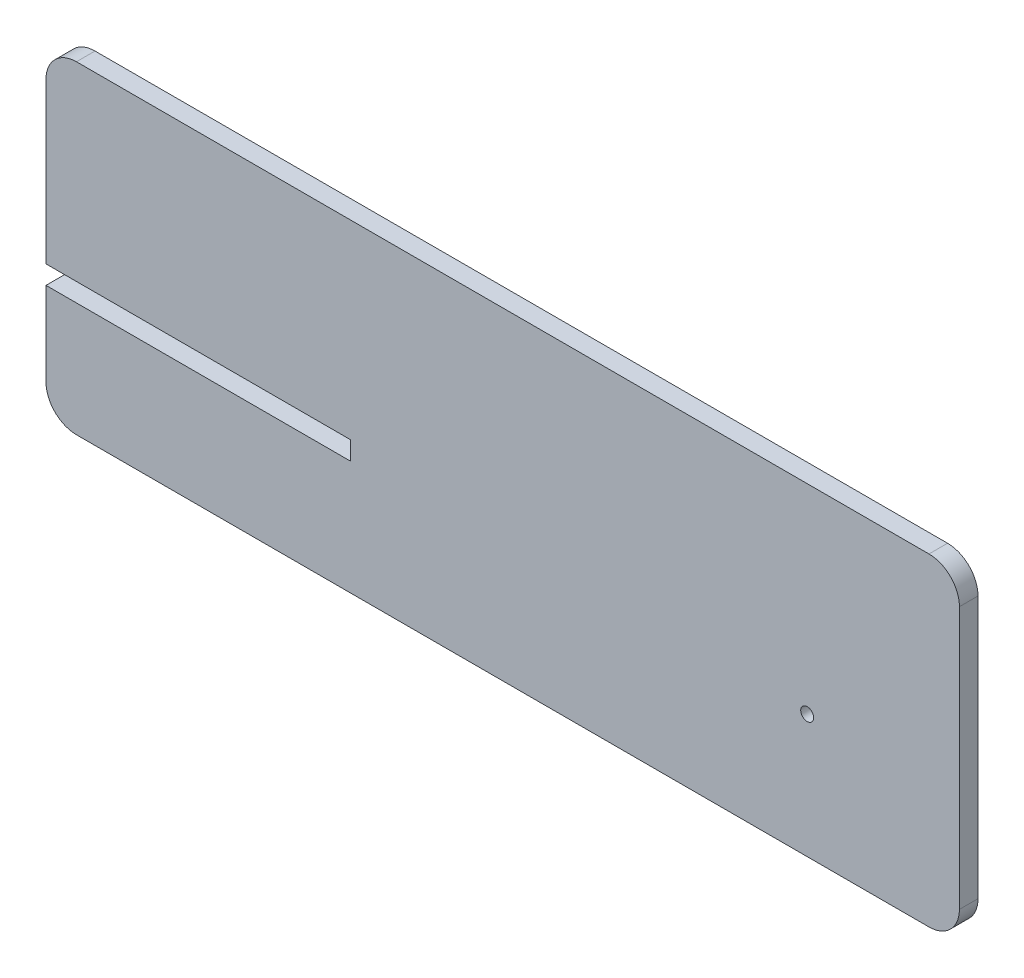
SolidWorks part; units mm, degrees
material "Corrugated Paper"
ref_plane "Front Plane" through (0, 0, 0) normal (0, 0, 1) x (1, 0, 0)
ref_plane "Top Plane" through (0, 0, 0) normal (0, 1, 0) x (1, 0, 0)
ref_plane "Right Plane" through (0, 0, 0) normal (1, 0, 0) x (0, 0, -1)
sketch "Sketch2" plane through (0, 0, 0) normal (0, 0, 1) x (1, 0, 0)
  line L0 (-50.8, 1.5494) -> (-50.8, 7.8994)
  line L1 (-50.8, -7.8994) -> (50.8, -7.8994)
  line L2 (-50.8, -7.8994) -> (-50.8, -1.5494)
  line L3 (-50.8, 7.8994) -> (50.8, 7.8994)
  line L4 (50.8, -7.8994) -> (50.8, 7.8994)
  line L5 (-50.8, -7.8994) -> (50.8, 7.8994) construction
  line L6 (-50.8, 7.8994) -> (50.8, -7.8994) construction
  line L7 (-50.8, 1.5494) -> (0, 1.5494)
  line L9 (-50.8, -1.5494) -> (0, -1.5494)
  line L10 (0, 1.5494) -> (0, -1.5494)
  point P0 (0, 0)
  dimension "D1" = 50.8
  dimension "D3" = 3.0988
  dimension "D2" = 6.35
extrude "Boss-Extrude1" add sketch "Sketch2" along normal blind 3.0988
sketch "Sketch3" plane through (0, 0, 0) normal (0, 0, 1) x (1, 0, 0)
  line L0 (-50.8, -7.8994) -> (-50.8, -20.5994)
  line L1 (-50.8, -20.5994) -> (101.6, -20.5994)
  line L2 (101.6, -20.5994) -> (101.6, 33.2994)
  line L3 (50.8, 7.8994) -> (-50.8, 7.8994) construction
  line L5 (-50.8, 33.2994) -> (-50.8, 7.8994)
  line L6 (-50.8, -7.8994) -> (50.8, -7.8994) construction
  line L7 (50.8, -7.8994) -> (50.8, 7.8994) construction
  line L8 (-50.8, -7.8994) -> (50.8, -7.8994)
  line L9 (50.8, -7.8994) -> (50.8, 7.8994)
  line L10 (50.8, 7.8994) -> (-50.8, 7.8994)
  line L13 (101.6, 33.2994) -> (-50.8, 33.2994)
  circle A0 centre (76.2, 0) radius 1.0795
  point P2 (0, 0)
  point P3 (101.6, 34.4903)
  dimension "D1" = 2.159
  dimension "D2" = 12.7
  dimension "D3" = 25.4
  dimension "D4" = 152.4
  dimension "D5" = 25.4
extrude "Boss-Extrude2" add sketch "Sketch3" along normal blind 3.0988 contours L10 L9 L8 L0 L1 L2 L5 A0 region at (0, -9.5159, 0)
fillet "Fillet1" radius 5.08 4 edges at (101.6, -20.5994, 1.5494) (-50.8, -20.5994, 1.5494) (-50.8, 33.2994, 1.5494) (101.6, 33.2994, 1.5494)
equation "\"rodThick\"= 0.085in"
equation "\"thick\"= 0.122in"
equation "\"clear\"= 0.003in"
equation "\"D3@Sketch2\"=\"thick\""
equation "\"D1@Boss-Extrude1\"=\"thick\""
equation "\"D1@Sketch3\"=\"rodThick\""
equation "\"D1@Boss-Extrude2\"=\"thick\""
